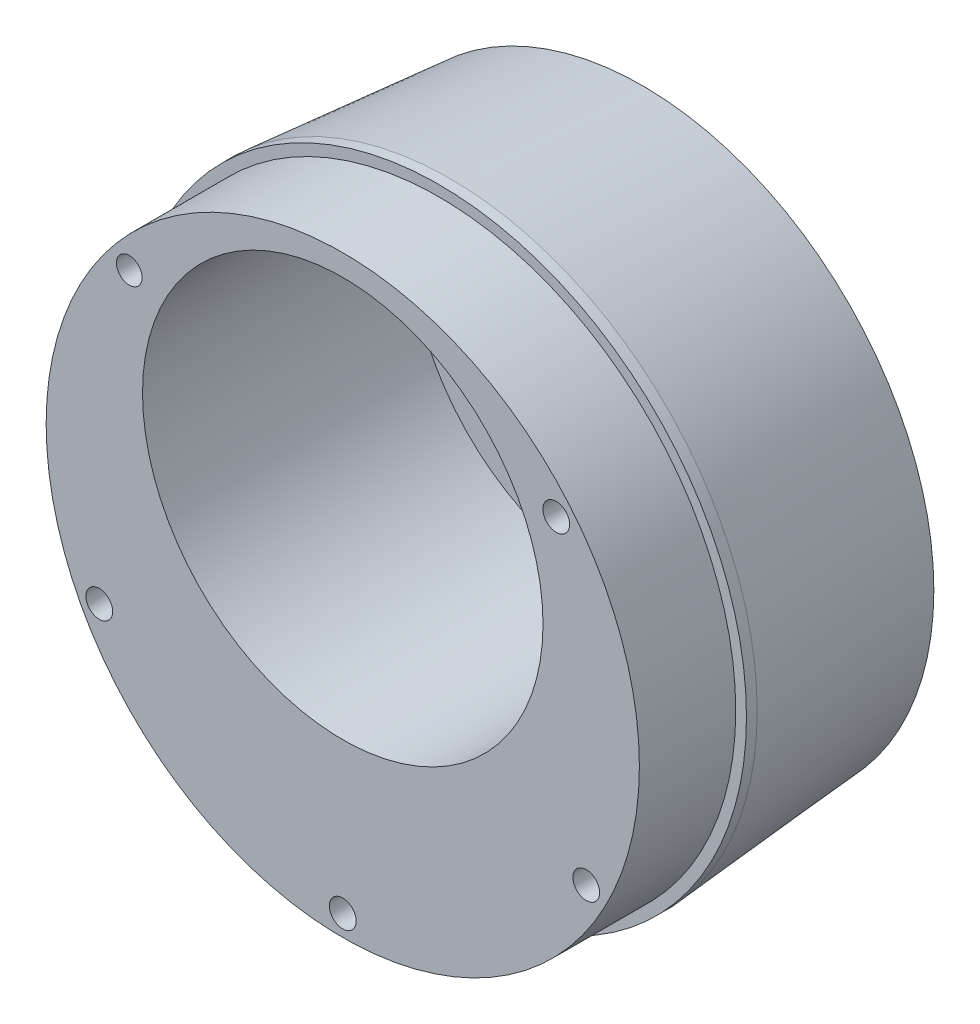
SolidWorks part; units mm, degrees
ref_plane "Спереди" through (0, 0, 0) normal (0, 0, 1) x (1, 0, 0)
ref_plane "Сверху" through (0, 0, 0) normal (0, 1, 0) x (1, 0, 0)
ref_plane "Справа" through (0, 0, 0) normal (1, 0, 0) x (0, 0, -1)
sketch "Sketch1" plane through (0, 0, 0) normal (0, 0, 1) x (1, 0, 0)
  circle A0 centre (0, 0) radius 28.7
  circle A1 centre (0, 0) radius 6.15
  circle A3 centre (0, 7) radius 15.5 construction
  circle A4 centre (15.5, 7) radius 1.65
  circle A5 centre (7.75, -6.4234) radius 1.65
  circle A6 centre (-7.75, -6.4234) radius 1.65
  circle A7 centre (-15.5, 7) radius 1.65
  circle A8 centre (-7.75, 20.4234) radius 1.65
  circle A9 centre (7.75, 20.4234) radius 1.65
  point P20 (0, 7)
  dimension "D1" = 57.4
  dimension "D2" = 12.3
  dimension "D3" = 7
  dimension "D4" = 31
  dimension "D5" = 3.3
  dimension "D6" = 6
extrude "Основа" add sketch "Sketch1" along normal blind 28
sketch "Sketch2" plane through (0, 0, 28) normal (0, 0, 1) x (1, 0, 0)
  circle A0 centre (0, 7) radius 18.7
  dimension "D1" = 37.4
  dimension "D2" = 7
extrude "Посадочное под двигатель" cut sketch "Sketch2" against normal offset from surface (25 mm away) 3 up to face at (28.7, 0, 0)
sketch "Sketch4" plane through (0, 0, 28) normal (0, 0, 1) x (1, 0, 0)
  circle A0 centre (0, 0) radius 27.7
  circle A1 centre (0, 0) radius 28.7
  circle A2 centre (0, 0) radius 28.7 construction
  dimension "D1" = 55.4
extrude "Вырез под внутреннее кольцо подшипника" cut sketch "Sketch4" against normal blind 9
sketch "Sketch5" plane through (0, 0, 28) normal (0, 0, 1) x (1, 0, 0)
  line L0 (0, 7) -> (0, -25.75) construction
  line L1 (-22.74, -12.0811) -> (0, 7) construction
  line L2 (0, 7) -> (-19.9369, 16.2967) construction
  circle A1 centre (0, 7) radius 18.7 construction
  circle A3 centre (-22.74, -12.0811) radius 1.25
  circle A12 centre (0, 0) radius 25.75 construction
  circle A13 centre (0, 7) radius 18.7 construction
  circle A14 centre (0, -25.75) radius 1.25
  circle A15 centre (19.9369, 16.2967) radius 1.25
  circle A16 centre (22.74, -12.0811) radius 1.25
  circle A17 centre (-19.9369, 16.2967) radius 1.2
  dimension "D1" = 51.5
  dimension "D4" = 2.5
  dimension "D5" = 2.4
  dimension "D2" = 50
  dimension "D3" = 115
extrude "Под шурупы крепления шайбы колена" cut sketch "Sketch5" against normal blind 10
sketch "Эскиз1" plane through (0, 0, 0) normal (0, 0, -1) x (-1, 0, 0)
  circle A0 centre (-7.75, 20.4234) radius 3
  circle A1 centre (7.75, 20.4234) radius 3
  circle A2 centre (15.5, 7) radius 3
  circle A3 centre (7.75, -6.4234) radius 3
  circle A4 centre (-7.75, -6.4234) radius 3
  circle A5 centre (-15.5, 7) radius 3
  dimension "D1" = 6
extrude "Углубления под шляпки" cut sketch "Эскиз1" against normal blind 0.5
chamfer "Скругления под шляпки винтов крепления двигателя к стакану" distance 1.5 angle 45 6 edges at (13.85, 7, 0.5) (6.1, -6.4234, 0.5) (-9.4, -6.4234, 0.5) (-17.15, 7, 0.5) (-9.4, 20.4234, 0.5) (6.1, 20.4234, 0.5)
chamfer "Фаска1" distance 1.5 distance2 18 1 edges at (28.7, 0, 0) first distance on face at (12.5, 7, 0)
